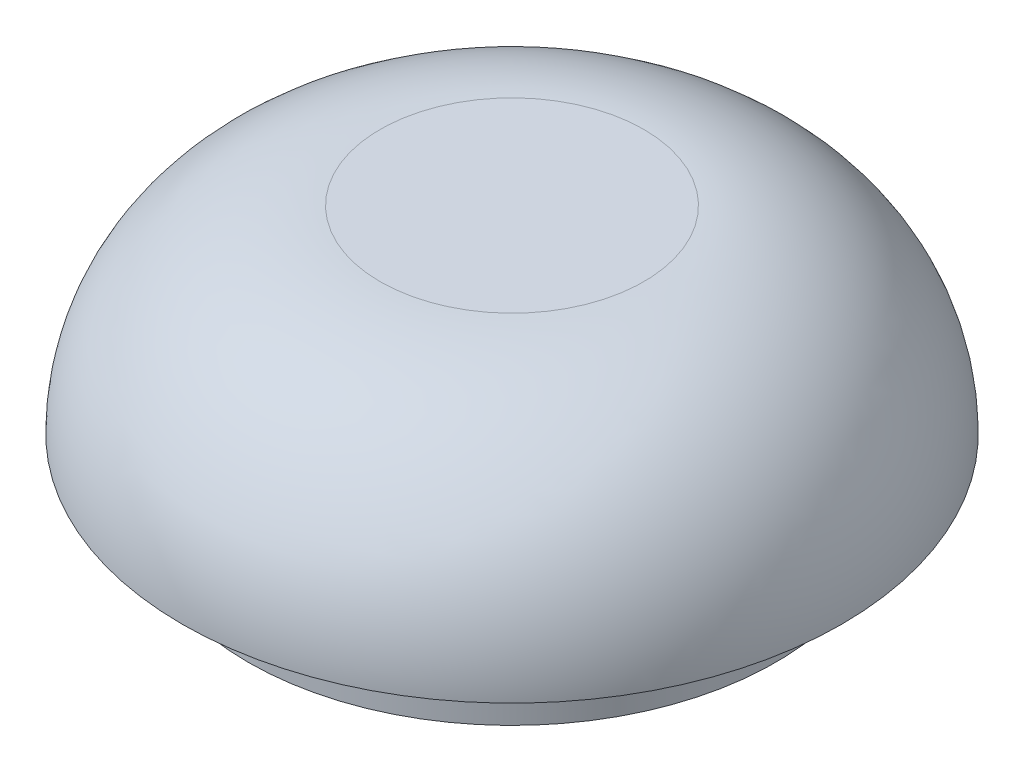
SolidWorks part; units mm, degrees
ref_plane "Front Plane" through (0, 0, 0) normal (0, 0, 1) x (1, 0, 0)
ref_plane "Top Plane" through (0, 0, 0) normal (0, 1, 0) x (1, 0, 0)
ref_plane "Right Plane" through (0, 0, 0) normal (1, 0, 0) x (0, 0, -1)
sketch "Sketch1" plane through (0, 0, 0) normal (0, 1, 0) x (1, 0, 0)
  circle A0 centre (0, 0) radius 5
  dimension "D1" = 10
extrude "Boss-Extrude1" add sketch "Sketch1" along normal blind 3
sketch "Sketch2" plane through (0, 0, 0) normal (0, -1, 0) x (1, 0, 0)
  circle A0 centre (0, 0) radius 4
  dimension "D1" = 8
extrude "Boss-Extrude2" add sketch "Sketch2" along normal blind 1
fillet "Fillet1" radius 3 1 edges at (0, 3, 5)
